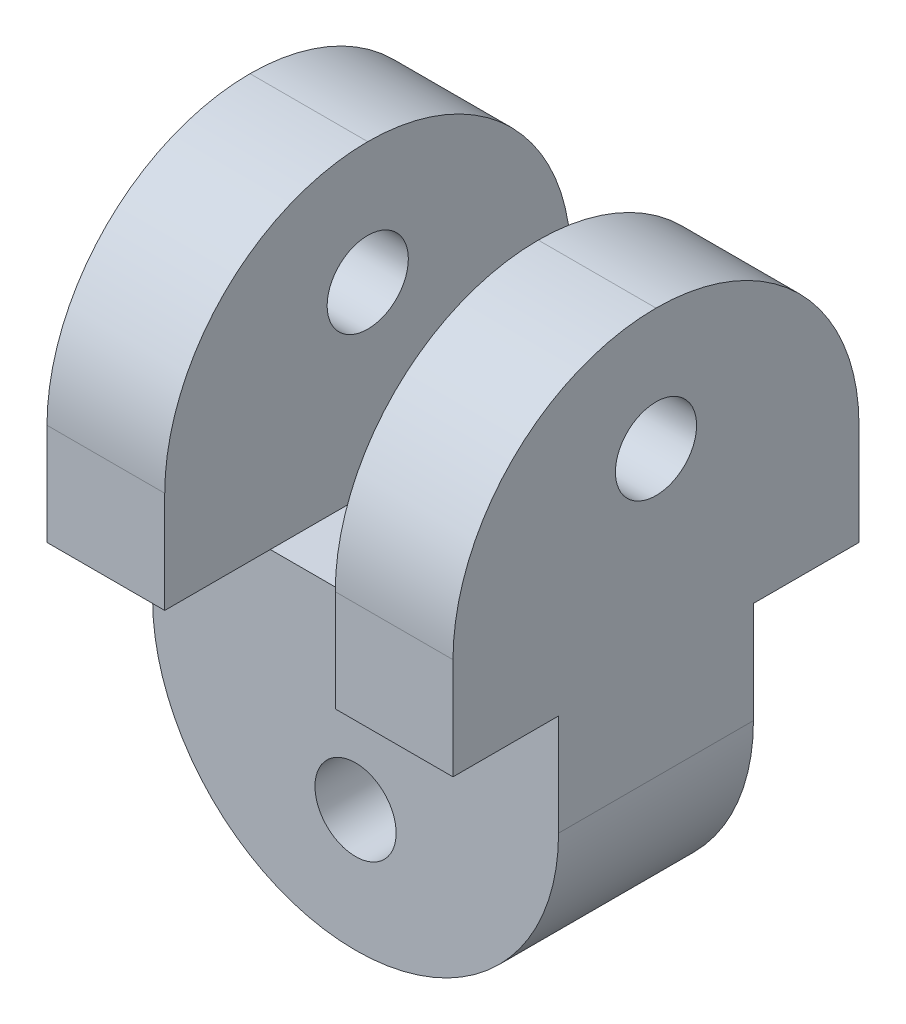
SolidWorks part; units mm, degrees
ref_plane "Front Plane" through (0, 0, 0) normal (0, 0, 1) x (1, 0, 0)
ref_plane "Top Plane" through (0, 0, 0) normal (0, 1, 0) x (1, 0, 0)
ref_plane "Right Plane" through (0, 0, 0) normal (1, 0, 0) x (0, 0, -1)
sketch "Sketch1" plane through (0, 0, 0) normal (0, 0, 1) x (1, 0, 0)
  line L0 (0, 7.5) -> (0, -7.5) construction
  line L1 (-5, -7.5) -> (5, -7.5)
  line L2 (-5, -7.5) -> (-5, 7.5)
  line L3 (-5, 7.5) -> (5, 7.5) construction
  line L4 (5, -7.5) -> (5, 7.5)
  line L5 (-5, -7.5) -> (5, 7.5) construction
  line L6 (-5, 7.5) -> (5, -7.5) construction
  line L7 (-2.1, 7.5) -> (-2.1, 0)
  line L8 (-2.1, 0) -> (2.1, 0)
  line L9 (-2.1, 7.5) -> (-5, 7.5)
  line L10 (2.1, 7.5) -> (5, 7.5)
  line L11 (2.1, 7.5) -> (2.1, 0)
  circle A0 centre (0, -4.5) radius 1
  point P0 (0, 0)
  point P12 (0, 0)
  dimension "D4" = 2
  dimension "D5" = 3
  dimension "D1" = 10
  dimension "D2" = 15
  dimension "D3" = 2.1
extrude "Boss-Extrude1" add sketch "Sketch1" along normal blind 10
sketch "Sketch2" plane through (5, 0, 0) normal (1, 0, 0) x (0, 0, -1)
  line L6 (-7.4, 0) -> (-2.6, 0) construction
  line L7 (-10, -7.5) -> (-7.4, -7.5)
  line L8 (-10, -7.5) -> (-10, 0)
  line L9 (-10, 0) -> (-7.4, 0)
  line L10 (-7.4, -7.5) -> (-7.4, 0)
  line L11 (0, -7.5) -> (-2.6, -7.5)
  line L12 (0, -7.5) -> (0, 0)
  line L13 (0, 0) -> (-2.6, 0)
  line L14 (-2.6, -7.5) -> (-2.6, 0)
  line L15 (-5, 7.5) -> (-5, -7.5) construction
  line L16 (-10, 7.5) -> (0, 7.5) construction
  line L17 (-10, -7.5) -> (0, -7.5) construction
  circle A0 centre (-5, 4.5) radius 1
  point P16 (-5, 0)
  dimension "D3" = 2
  dimension "D1" = 4.8
  dimension "D2" = 7.5
  dimension "D4" = 3
extrude "Cut-Extrude1" cut sketch "Sketch2" against normal blind 10
fillet "Fillet1" radius 5 6 edges at (-5, -7.5, 5) (5, -7.5, 5) (-3.55, 7.5, 0) (3.55, 7.5, 0) (3.55, 7.5, 10) (-3.55, 7.5, 10)
